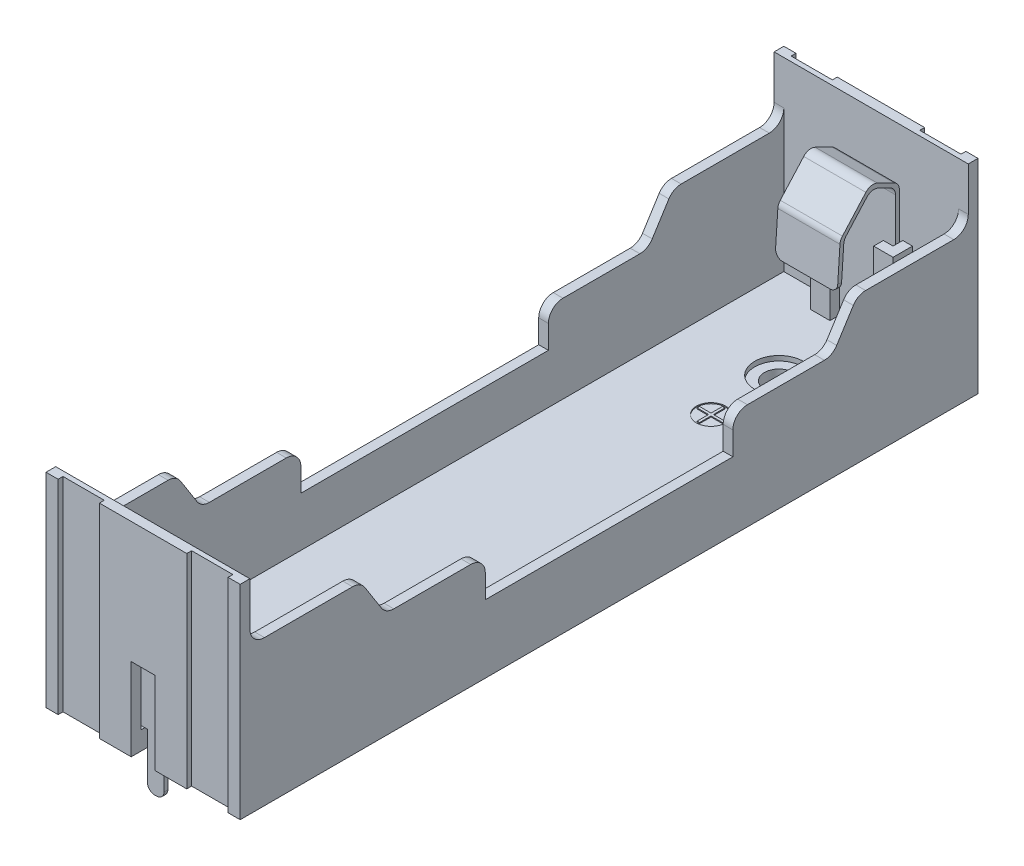
SolidWorks part; units mm, degrees
material "ABS"
ref_plane "Спереди" through (0, 0, 0) normal (0, 0, 1) x (1, 0, 0)
ref_plane "Сверху" through (0, 0, 0) normal (0, 1, 0) x (1, 0, 0)
ref_plane "Справа" through (0, 0, 0) normal (1, 0, 0) x (0, 0, -1)
other "Configuration Table"
sketch "Эскиз1" plane through (0, 0, 0) normal (0, 1, 0) x (1, 0, 0)
  line L1 (-10, 38) -> (10, 38)
  line L2 (-10, 38) -> (-10, -38)
  line L3 (-10, -38) -> (10, -38)
  line L4 (10, 38) -> (10, -38)
  line L5 (-10, 38) -> (10, -38) construction
  line L6 (-10, -38) -> (10, 38) construction
  point P0 (0, 0)
  dimension "D1" = 76
  dimension "D2" = 20
extrude "Основа" add sketch "Эскиз1" along normal blind 21
sketch "Эскиз2" plane through (0, 0, 0) normal (0, 1, 0) x (1, 0, 0)
  line L1 (10, 38) -> (-10, 38) construction
  line L2 (-4.5, 38) -> (-4.5, 37.5)
  line L3 (-4.5, 37.5) -> (-8.75, 37.5)
  line L4 (-8.75, 37.5) -> (-8.75, 38)
  line L5 (-8.75, 38) -> (-10.75, 38)
  line L6 (-10.75, 38) -> (-10.75, 37.5)
  line L13 (-10.75, 38) -> (-10, 38)
  line L14 (-10, 38) -> (-10, 46.5071)
  line L15 (-10, 46.5071) -> (10, 46.5071)
  line L16 (0, 46.5071) -> (0, 38)
  line L17 (4.5, 38) -> (-4.5, 38)
  line L18 (10, 38) -> (10, 46.5071)
  line L26 (10.75, 38) -> (10.75, 37.5)
  line L27 (8.75, 38) -> (10.75, 38)
  line L28 (4.5, 38) -> (4.5, 37.5)
  line L29 (4.5, 37.5) -> (8.75, 37.5)
  line L30 (8.75, 37.5) -> (8.75, 38)
  line L31 (10.75, 38) -> (10, 38)
  line L32 (-10.75, 37.5) -> (-8.75, 37.5)
  line L33 (10.75, 37.5) -> (8.75, 37.5)
  point P22 (0, 38)
  dimension "D1" = 9
  dimension "D2" = 2
  dimension "D3" = 4.25
  dimension "D4" = 0.5
extrude "Рёбра" cut sketch "Эскиз2" along normal through all contours L29 L30 L27 L26 L18 L15 L16 L17 L28 | L17 L16 L15 L14 L13 L6 L5 L4 L3 L2 region at (-5.0396, 0, -42.1438) region at (5.0396, 0, -42.1438)
mirror "Зеркальное отражение1" about plane through (0, 0, 0) normal (0, 0, 1) of "Рёбра"
sketch "Эскиз3" plane through (0, 21, 0) normal (0, 1, 0) x (1, 0, 0)
  line L0 (9, 0) -> (-9, 0) construction
  line L1 (9, 37) -> (-9, 37)
  line L2 (9, 37) -> (9, -37)
  line L3 (9, -37) -> (-9, -37)
  line L4 (-9, 37) -> (-9, -37)
  line L5 (9, 37) -> (-9, -37) construction
  line L6 (9, -37) -> (-9, 37) construction
  point P0 (0, 0)
  point P9 (0, 0)
  dimension "D1" = 18
  dimension "D2" = 74
extrude "Отсеки" cut sketch "Эскиз3" against normal blind 19.1
sketch "Эскиз4" plane through (0, 0, 0) normal (1, 0, 0) x (0, 0, -1)
  line L0 (37, 21) -> (-37, 21) construction
  line L1 (37, 27) -> (-37, 27)
  line L2 (37, 27) -> (37, 15)
  line L3 (37, 15) -> (-37, 15)
  line L4 (-37, 27) -> (-37, 15)
  line L5 (37, 27) -> (-37, 15) construction
  line L6 (37, 15) -> (-37, 27) construction
  line L7 (-37, 1.9) -> (-37, 21) construction
  point P0 (0, 21)
  dimension "D1" = 15
extrude "Уменьшение внутренних стенок" cut sketch "Эскиз4" against normal blind 15 and the other way blind 15
sketch "Эскиз5" plane through (10, 0, 0) normal (1, 0, 0) x (0, 0, -1)
  line L0 (-38, 21) -> (-35.6, 21)
  line L1 (-38, 21) -> (-37, 21) construction
  line L2 (-35.6, 21) -> (-35.6, 15)
  line L3 (-35.6, 15) -> (-25.6, 15)
  line L4 (-25.6, 15) -> (-23, 10.9)
  line L5 (-23, 10.9) -> (-12.75, 10.9)
  line L6 (-12.75, 10.9) -> (-12.75, 7)
  line L7 (-12.75, 7) -> (12.75, 7)
  line L8 (0, 7) -> (0, 0) construction
  line L9 (-35.6, 21) -> (35.6, 21)
  line L10 (12.75, 10.9) -> (12.75, 7)
  line L11 (23, 10.9) -> (12.75, 10.9)
  line L12 (25.6, 15) -> (23, 10.9)
  line L13 (35.6, 15) -> (25.6, 15)
  line L14 (35.6, 21) -> (35.6, 15)
  line L15 (-38, 21) -> (-37, 21) construction
  point P14 (0, 0)
  point P20 (0, 21)
  point P23 (-38, 21)
  point P26 (-38, 21)
  line M12 (38, 21) -> (37, 21)
  dimension "D1" = 12.75
  dimension "D2" = 10.25
  dimension "D3" = 2.4
  dimension "D4" = 10
  dimension "D5" = 6
  dimension "D6" = 3.9
  dimension "D7" = 7
extrude "Уменьшение внешних стенок" cut sketch "Эскиз5" against normal blind 15 contours L14 L2 L3 L4 L5 L6 L7 L10 L11 L12 L13 M12 region at (10, 15.384, 0)
fillet "Скругление2" radius 1.5 8 edges at (9.5, 10.9, -23) (9.5, 10.9, -12.75) (9.5, 10.9, 12.75) (9.5, 10.9, 23) (9.5, 15, -37) (9.5, 15, -25.6) (9.5, 15, 37) (9.5, 15, 25.6)
mirror "Зеркальное отражение2" about plane through (0, 0, 0) normal (1, 0, 0) of "Скругление2", "Уменьшение внешних стенок"
sketch "Эскиз6" plane through (0, 0, 0) normal (0, 1, 0) x (1, 0, 0)
  line L0 (-4.5, -38) -> (4.5, -38) construction
  line L1 (-1.225, -41.5) -> (1.225, -41.5)
  line L2 (-1.225, -41.5) -> (-1.225, -34.5)
  line L3 (-1.225, -34.5) -> (1.225, -34.5)
  line L4 (1.225, -41.5) -> (1.225, -34.5)
  line L5 (-1.225, -41.5) -> (1.225, -34.5) construction
  line L6 (-1.225, -34.5) -> (1.225, -41.5) construction
  line L7 (-10, 0) -> (10, 0) construction
  line L8 (10, -38) -> (10, 38) construction
  line L27 (-1.225, 34.5) -> (1.225, 41.5) construction
  line L28 (-1.225, 41.5) -> (1.225, 34.5) construction
  line L37 (1.225, 41.5) -> (1.225, 34.5)
  line L38 (-1.225, 34.5) -> (1.225, 34.5)
  line L39 (-1.225, 41.5) -> (-1.225, 34.5)
  line L40 (-1.225, 41.5) -> (1.225, 41.5)
  point P0 (0, -38)
  point P10 (0, 0)
  point P13 (0, 0)
  point P15 (0, 0)
  point P16 (0, 0)
  point P17 (0, 0)
  point P42 (0, 38)
  dimension "D1" = 2.45
  dimension "D2" = 3.5
extrude "Вырезы под контакты" cut sketch "Эскиз6" along normal blind 8.5
sketch "Эскиз11" plane through (0, 0, 0) normal (0, 1, 0) x (1, 0, 0)
  line L0 (0, 27.5) -> (0, -27.5) construction
  line L1 (1.5, -27.5) -> (-1.5, -27.5) construction
  line L3 (1.5, 27.5) -> (-1.5, 27.5) construction
  circle A1 centre (0, 27.5) radius 1.5
  circle A4 centre (0, -27.5) radius 1.5
  point P0 (0, 0)
  point P6 (0, 0)
  point P9 (0, 0)
  point P10 (0, 0)
  point P13 (0, 0)
  point P14 (0, 0)
  dimension "D2" = 3
  dimension "D1" = 55
extrude "Крепежные отверстия" cut sketch "Эскиз11" along normal through all
sketch "Эскиз12" plane through (0, 0, 0) normal (0, 1, 0) x (1, 0, 0)
  circle A1 centre (0, 27.5) radius 1.5 construction
  circle A4 centre (0, -27.5) radius 1.5 construction
  circle A7 centre (0, 27.5) radius 1.5
  circle A10 centre (0, -27.5) radius 1.5
  circle A13 centre (0, 27.5) radius 2.8
  circle A16 centre (0, -27.5) radius 2.8
  point P18 (0, 0)
  dimension "D1" = 1.3
extrude "Юбки отверстий" add sketch "Эскиз12" against normal blind 0.3
sketch "Эскиз13" plane through (0, 1.9, 0) normal (0, 1, 0) x (1, 0, 0)
  circle A1 centre (0, -27.5) radius 1.5 construction
  circle A3 centre (0, 27.5) radius 1.5 construction
  circle A6 centre (0, -27.5) radius 1.5
  circle A8 centre (0, 27.5) radius 1.5
  circle A13 centre (0, -27.5) radius 2.5
  circle A15 centre (0, 27.5) radius 2.5
  point P0 (0, 0)
  dimension "D1" = 1
extrude "Вырез-Вытянуть17" cut sketch "Эскиз13" against normal blind 0.5
sketch "Эскиз14" plane through (0, 1.9, 0) normal (0, 1, 0) x (1, 0, 0)
  line L0 (0, 20.5) -> (0, -20.5) construction
  line L3 (1.5, 20.5) -> (0, 20.5) construction
  line L4 (0, -20.5) -> (0, -19) construction
  line L5 (0, 19) -> (0, 20.5) construction
  line L8 (0.125, -19.2) -> (-0.125, -19.2)
  line L9 (0.125, -19.2) -> (0.125, -21.8)
  line L10 (0.125, -21.8) -> (-0.125, -21.8)
  line L11 (-0.125, -19.2) -> (-0.125, -21.8)
  line L12 (0.125, -19.2) -> (-0.125, -21.8) construction
  line L13 (0.125, -21.8) -> (-0.125, -19.2) construction
  line L14 (0.125, 21.8) -> (-0.125, 21.8)
  line L15 (0.125, 21.8) -> (0.125, 19.2)
  line L16 (0.125, 19.2) -> (-0.125, 19.2)
  line L17 (-0.125, 21.8) -> (-0.125, 19.2)
  line L18 (0.125, 21.8) -> (-0.125, 19.2) construction
  line L19 (0.125, 19.2) -> (-0.125, 21.8) construction
  line L20 (1.3, 20.625) -> (-1.3, 20.625)
  line L21 (1.3, 20.625) -> (1.3, 20.375)
  line L22 (1.3, 20.375) -> (-1.3, 20.375)
  line L23 (-1.3, 20.625) -> (-1.3, 20.375)
  line L24 (1.3, 20.625) -> (-1.3, 20.375) construction
  line L25 (1.3, 20.375) -> (-1.3, 20.625) construction
  circle A0 centre (0, 20.5) radius 1.5
  circle A1 centre (0, -20.5) radius 1.5
  point P0 (0, 0)
  point P2 (0, 0)
  dimension "D2" = 3
  dimension "D3" = 2.6
  dimension "D4" = 0.25
  dimension "D5" = 41
extrude "Полярность" cut sketch "Эскиз14" against normal blind 0.1 contours A1 L11 L8 L9 L10 | A0 L23 L20 L17 L14 L15 L21 L22 L16 region at (-1.4576, 1.9, -20.5) region at (-1.4576, 1.9, 20.5)
sketch "Эскиз15" plane through (0, 1.9, 0) normal (0, 1, 0) x (1, 0, 0)
  line L0 (-1.225, 37) -> (-9, 37) construction
  line L1 (-1.225, 37) -> (-1.225, 34.5) construction
  line L16 (-2.25, 35) -> (-4.25, 35)
  line L17 (-4.25, 35) -> (-4.25, 37)
  line L18 (-4.25, 37) -> (-3.25, 37)
  line L19 (-3.25, 37) -> (-3.25, 36)
  line L20 (-3.25, 36) -> (-2.25, 36)
  line L21 (-2.25, 36) -> (-2.25, 35)
  line L22 (2.25, 35) -> (2.25, 36)
  line L23 (2.25, 36) -> (3.25, 36)
  line L24 (3.25, 36) -> (3.25, 37)
  line L25 (3.25, 37) -> (4.25, 37)
  line L26 (4.25, 37) -> (4.25, 35)
  line L27 (4.25, 35) -> (2.25, 35)
  line L28 (0, 35.5) -> (0, 35) construction
  line L29 (-2.25, 35) -> (2.25, 35) construction
  line L44 (10, 0) -> (-10, 0) construction
  line L45 (-10, -12.75) -> (-10, 12.75) construction
  line L48 (-2.25, -35) -> (2.25, -35) construction
  line L49 (0, -35.5) -> (0, -35) construction
  line L64 (4.25, -35) -> (2.25, -35)
  line L65 (4.25, -37) -> (4.25, -35)
  line L66 (3.25, -37) -> (4.25, -37)
  line L67 (3.25, -36) -> (3.25, -37)
  line L68 (2.25, -36) -> (3.25, -36)
  line L69 (2.25, -35) -> (2.25, -36)
  line L70 (-2.25, -36) -> (-2.25, -35)
  line L71 (-3.25, -36) -> (-2.25, -36)
  line L72 (-3.25, -37) -> (-3.25, -36)
  line L73 (-4.25, -37) -> (-3.25, -37)
  line L74 (-4.25, -35) -> (-4.25, -37)
  line L75 (-2.25, -35) -> (-4.25, -35)
  point P0 (0, 0)
  point P4 (19.5, 35)
  point P24 (0, 35)
  point P55 (0, 0)
  point P99 (0, -35)
  dimension "D1" = 2
  dimension "D2" = 1.025
  dimension "D4" = 8.5
extrude "Пазы для контактов" add sketch "Эскиз15" along normal blind 8.9
ref_plane "Для эскиза контактов" through (0, 0, 0) normal (-1, 0, 0) x (0, 0, 1)
sketch "Эскиз16" plane through (0, 0, 0) normal (-1, 0, 0) x (0, 0, 1)
  line L1 (-38, 21) -> (-38, 0) construction
  line L3 (-36.5, 17.26) -> (-36.5, 15.9523) construction
  line L4 (-36.5, 15.9523) -> (-33.8, 17.26)
  line L5 (-33.8, 17.26) -> (-30.8, 13.9059)
  line L6 (-30.8, 13.9059) -> (-30.5, 9.4159)
  line L7 (-36.5, 17.26) -> (-33.8, 17.26) construction
  line L8 (-36.5, 15.9523) -> (-36.5, 2)
  line L10 (-36.5, 2) -> (-36.5, -3.54) construction
  line L12 (-38, 0) -> (38, 0) construction
  point P2 (0, 0)
  point P4 (0, 0)
  point P8 (0, 0)
  point P12 (0, 0)
  point P18 (0, 0)
  dimension "D1" = 20.8
  dimension "D2" = 3
  dimension "D3" = 4.5
  dimension "D4" = 6
  dimension "D5" = 5.7
  dimension "D6" = 2.7
  dimension "D7" = 2
  dimension "D8" = 1.5
  dimension "D9" = 13.9523
extrude "Контакт" add sketch "Эскиз16" along normal mid plane 6.4 thin thin type mid plane wall 0.4
sketch "Эскиз17" plane through (0, 2, 0) normal (0, -1, 0) x (1, 0, 0)
  line L0 (0, -36.7) -> (0, -36.3) construction
  line L1 (-3.2, -36.7) -> (3.2, -36.7) construction
  line L2 (-3.2, -36.3) -> (3.2, -36.3) construction
  line L4 (0.85, -36.3) -> (-0.85, -36.3)
  line L5 (0.85, -36.3) -> (0.85, -36.7)
  line L6 (0.85, -36.7) -> (-0.85, -36.7)
  line L7 (-0.85, -36.3) -> (-0.85, -36.7)
  line L8 (0.85, -36.3) -> (-0.85, -36.7) construction
  line L9 (0.85, -36.7) -> (-0.85, -36.3) construction
  point P6 (0, -36.5)
  dimension "D1" = 1.7
extrude "Штырёк для пайки" add sketch "Эскиз17" along normal blind 5.5
fillet "Скругление3" radius 1 6 edges at (0, 13.8239, -30.995) (0, 13.9879, -30.605) (0, 17.0143, -33.8485) (0, 17.5057, -33.7515) (0, 15.827, -36.3) (0, 16.0777, -36.7)
fillet "Скругление4" radius 0.75 6 edges at (3.2, 2, -36.5) (0.85, -3.5, -36.5) (-0.85, -3.5, -36.5) (-3.2, 2, -36.5) (3.2, 9.4159, -30.5) (-3.2, 9.4159, -30.5)
mirror "Mirror1" about plane through (0, 0, 0) normal (0, 0, 1) of bodies 125
equation "\"D1@Эскиз5\"=25.5/2"
